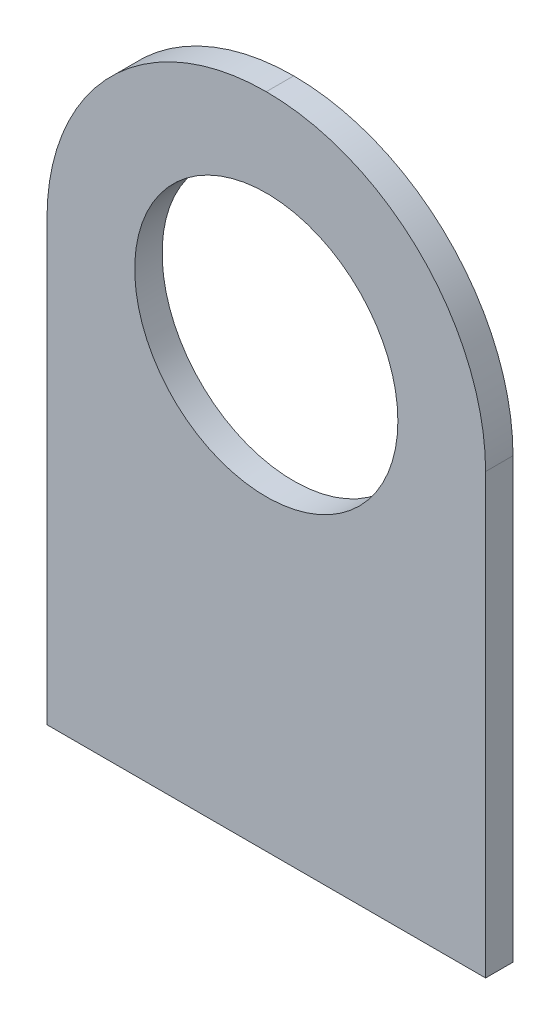
SolidWorks part; units mm, degrees
ref_plane "Front Plane" through (0, 0, 0) normal (0, 0, 1) x (1, 0, 0)
ref_plane "Top Plane" through (0, 0, 0) normal (0, 1, 0) x (1, 0, 0)
ref_plane "Right Plane" through (0, 0, 0) normal (1, 0, 0) x (0, 0, -1)
sketch "Sketch1" plane through (0, 0, 0) normal (0, 0, 1) x (1, 0, 0)
  line L1 (-102.3257, -2.8303) -> (-51.5257, -2.8303)
  line L2 (-102.3257, -2.8303) -> (-102.3257, -79.0303)
  line L3 (-102.3257, -79.0303) -> (-51.5257, -79.0303)
  line L4 (-51.5257, -2.8303) -> (-51.5257, -79.0303)
  circle A0 centre (-76.9257, -28.2303) radius 15.24
  dimension "D1" = 30.48
  dimension "D2" = 50.8
  dimension "D3" = 25.4
  dimension "D4" = 25.4
  dimension "D5" = 50.8
extrude "Boss-Extrude1" add sketch "Sketch1" along normal blind 3.175
fillet "Fillet1" radius 25.4 2 edges at (-102.3257, -2.8303, 1.5875) (-51.5257, -2.8303, 1.5875)
